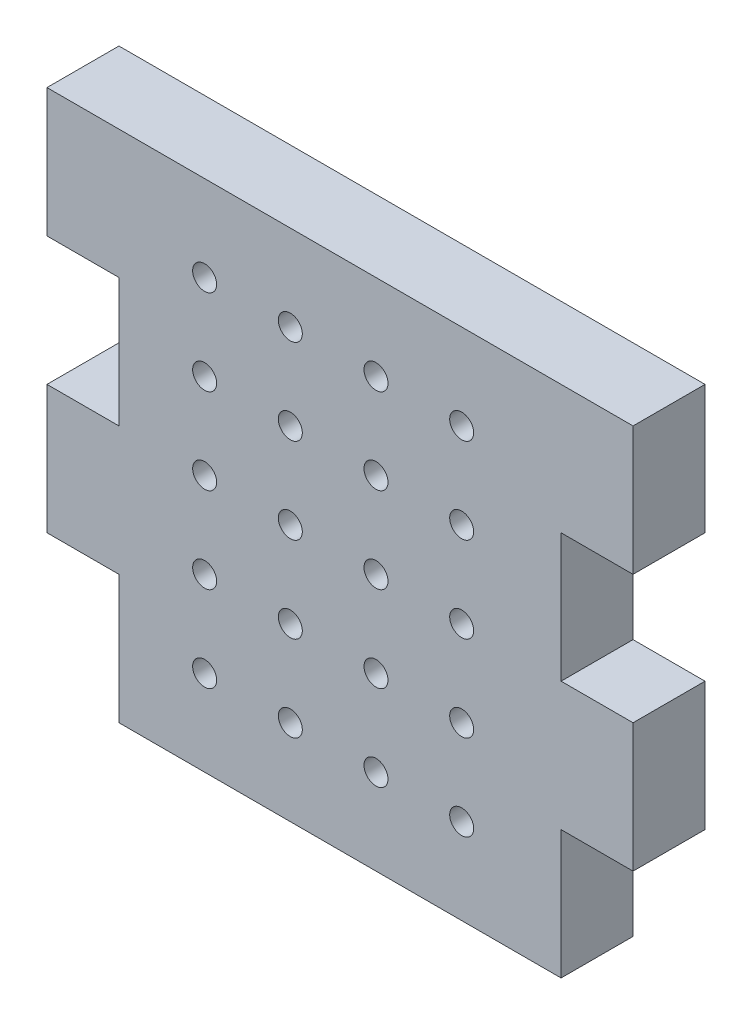
SolidWorks part; units mm, degrees
ref_plane "Front Plane" through (0, 0, 0) normal (0, 0, 1) x (1, 0, 0)
ref_plane "Top Plane" through (0, 0, 0) normal (0, 1, 0) x (1, 0, 0)
ref_plane "Right Plane" through (0, 0, 0) normal (1, 0, 0) x (0, 0, -1)
sketch "Sketch1" plane through (0, 0, 0) normal (0, 0, 1) x (1, 0, 0)
  line L1 (-88.0852, 14.1109) -> (-44.6512, 14.1109)
  line L2 (-88.0852, 14.1109) -> (-88.0852, -23.9891)
  line L3 (-88.0852, -23.9891) -> (-44.6512, -23.9891)
  line L4 (-44.6512, 14.1109) -> (-44.6512, -23.9891)
  dimension "D1" = 38.1
  dimension "D2" = 43.434
extrude "Boss-Extrude1" add sketch "Sketch1" along normal blind 5.334
sketch "Sketch2" plane through (0, 0, 5.334) normal (0, 0, 1) x (1, 0, 0)
  line L0 (-88.0852, 14.1109) -> (-88.0852, -23.9891) construction
  line L1 (-88.0852, -23.9891) -> (-82.7512, -23.9891)
  line L2 (-88.0852, -23.9891) -> (-88.0852, -14.4641)
  line L3 (-88.0852, -14.4641) -> (-82.7512, -14.4641)
  line L4 (-82.7512, -23.9891) -> (-82.7512, -14.4641)
  line L5 (-88.0852, -4.9391) -> (-82.7512, -4.9391)
  line L6 (-88.0852, -4.9391) -> (-88.0852, 4.5859)
  line L7 (-88.0852, 4.5859) -> (-82.7512, 4.5859)
  line L8 (-82.7512, -4.9391) -> (-82.7512, 4.5859)
  line L9 (-82.7512, 4.5859) -> (-82.7512, 14.1109) construction
  line L10 (-44.6512, 14.1109) -> (-88.0852, 14.1109) construction
  line L11 (-82.7512, -4.9391) -> (-82.7512, -14.4641) construction
  line L12 (-66.3682, 14.1109) -> (-66.3682, -23.9891) construction
  line L13 (-88.0852, -23.9891) -> (-44.6512, -23.9891) construction
  line L14 (-49.9852, -4.9391) -> (-49.9852, -14.4641) construction
  line L15 (-49.9852, 4.5859) -> (-49.9852, 14.1109) construction
  line L16 (-49.9852, -4.9391) -> (-49.9852, 4.5859)
  line L17 (-44.6512, 4.5859) -> (-49.9852, 4.5859)
  line L18 (-44.6512, -4.9391) -> (-44.6512, 4.5859)
  line L19 (-44.6512, -4.9391) -> (-49.9852, -4.9391)
  line L20 (-49.9852, -23.9891) -> (-49.9852, -14.4641)
  line L21 (-44.6512, -14.4641) -> (-49.9852, -14.4641)
  line L22 (-44.6512, -23.9891) -> (-44.6512, -14.4641)
  line L23 (-44.6512, -23.9891) -> (-49.9852, -23.9891)
  dimension "D1" = 5.334
extrude "Cut-Extrude1" cut sketch "Sketch2" against normal through all
sketch "Sketch3" plane through (0, 0, 5.334) normal (0, 0, 1) x (1, 0, 0)
  line L0 (-44.6512, 14.1109) -> (-88.0852, 14.1109) construction
  line L1 (-82.7512, -4.9391) -> (-82.7512, 4.5859) construction
  circle A0 centre (-76.4012, 7.7609) radius 0.889
  circle A1 centre (-70.0512, 7.7609) radius 0.889
  circle A2 centre (-63.7012, 7.7609) radius 0.889
  circle A3 centre (-57.3512, 7.7609) radius 0.889
  circle A4 centre (-76.4012, 1.4109) radius 0.889
  circle A5 centre (-70.0512, 1.4109) radius 0.889
  circle A6 centre (-63.7012, 1.4109) radius 0.889
  circle A7 centre (-57.3512, 1.4109) radius 0.889
  circle A8 centre (-76.4012, -4.9391) radius 0.889
  circle A9 centre (-70.0512, -4.9391) radius 0.889
  circle A10 centre (-63.7012, -4.9391) radius 0.889
  circle A11 centre (-57.3512, -4.9391) radius 0.889
  circle A12 centre (-76.4012, -11.2891) radius 0.889
  circle A13 centre (-70.0512, -11.2891) radius 0.889
  circle A14 centre (-63.7012, -11.2891) radius 0.889
  circle A15 centre (-57.3512, -11.2891) radius 0.889
  circle A16 centre (-76.4012, -17.6391) radius 0.889
  circle A17 centre (-70.0512, -17.6391) radius 0.889
  circle A18 centre (-63.7012, -17.6391) radius 0.889
  circle A19 centre (-57.3512, -17.6391) radius 0.889
  dimension "D1" = 1.778
  dimension "D2" = 6.35
  dimension "D3" = 6.35
  dimension "D4" = 4
  dimension "D5" = 5
extrude "Cut-Extrude2" cut sketch "Sketch3" against normal through all
equation "\"MDF\"= .21in"
equation "\"Foamcore\"= .13in"
equation "\"Gmaterial\"= \"MDF\""
equation "\"D1@Boss-Extrude1\"=\"MDF\""
equation "\"D1@Sketch2\"=\"MDF\""
equation "\"D2@Sketch1\"=\"MDF\"+\"MDF\"+1.29"
